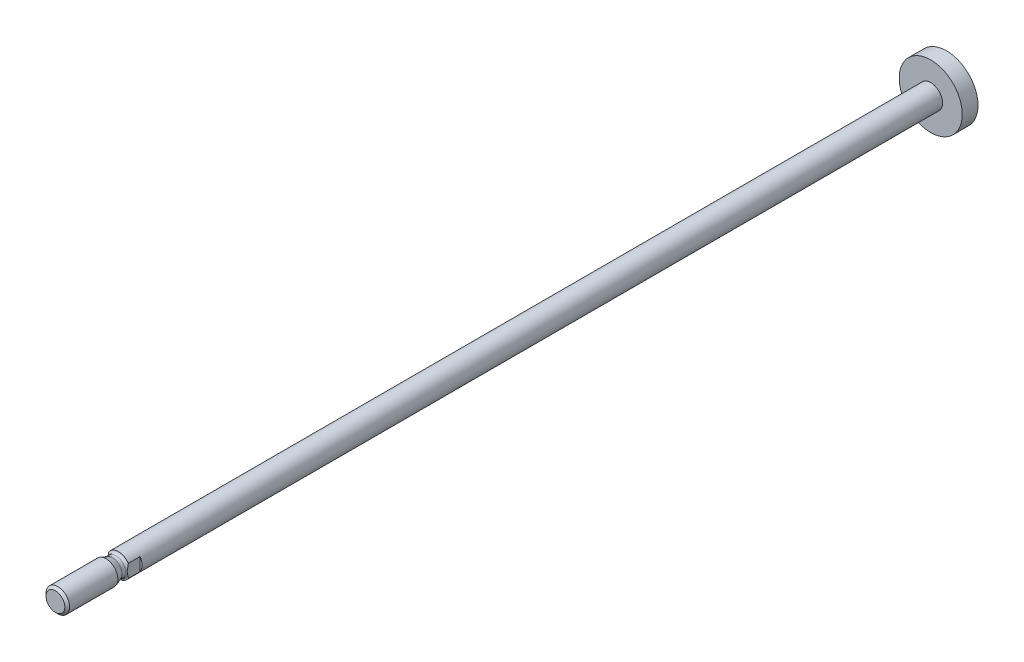
SolidWorks part; units mm, degrees
ref_plane "Ebene vorne" through (0, 0, 0) normal (0, 0, 1) x (1, 0, 0)
ref_plane "Ebene oben" through (0, 0, 0) normal (0, 1, 0) x (1, 0, 0)
ref_plane "Ebene rechts" through (0, 0, 0) normal (1, 0, 0) x (0, 0, -1)
sketch "Skizze1" plane through (0, 0, 0) normal (1, 0, 0) x (0, 0, -1)
  line L0 (-5, 0) -> (-5, 3)
  line L1 (-5, 3) -> (201.2, 3)
  line L2 (201.2, 3) -> (201.2, 8)
  line L3 (201.2, 8) -> (205.2, 8)
  line L4 (205.2, 8) -> (205.2, 0)
  line L5 (205.2, 0) -> (-5, 0)
  line L6 (205.2, 0) -> (-5, 0) construction
revolve "Rotation1" add sketch "Skizze1" angle 360 about L6 reverse direction yes
sketch "Skizze2" plane through (0, 0, 0) normal (1, 0, 0) x (0, 0, -1)
  line L0 (-21, 0) -> (-21, 2.3865)
  line L1 (-21, 2.3865) -> (-20.3865, 3)
  line L2 (-20.3865, 3) -> (-8.1485, 3)
  line L3 (-8.1485, 3) -> (-6.5994, 2.4362)
  line L4 (-6.3942, 2.4) -> (-5.6, 2.4)
  line L5 (-5, 3) -> (-4, 3)
  line L6 (-4, 3) -> (-4, 0)
  line L7 (-4, 0) -> (-21, 0)
  line L8 (-4, 0) -> (-21, 0) construction
  arc A0 (-6.5994, 2.4362) -> (-6.3942, 2.4) centre (-6.3942, 3) ccw
  arc A1 (-5.6, 2.4) -> (-5, 3) centre (-5.6, 3) ccw
revolve "Rotation2" add sketch "Skizze2" angle 360 about L8 reverse direction yes
cosmetic thread "Gewindedarstellung1" parameters "D1"=12.8515, "D2"=4.773
ref_plane "Ebene1" through (0, 0, 5) normal (0, 0, 1) x (1, 0, 0)
ref_plane "Ebene2" through (0, 0, 2) normal (0, 0, 1) x (1, 0, 0)
sketch "Skizze3" plane through (0, 0, 2) normal (0, 0, 1) x (1, 0, 0)
  line L0 (-5, 10) -> (-5, -5)
  line L1 (-5, -5) -> (-2.5, -5)
  line L2 (-2.5, -5) -> (-2.5, 5)
  line L3 (-2.5, 5) -> (2.5, 5)
  line L4 (2.5, 5) -> (2.5, -5)
  line L5 (2.5, -5) -> (5, -5)
  line L6 (5, -5) -> (5, 10)
  line L7 (5, 10) -> (-5, 10)
extrude "Schnitt-Linear austragen1" cut sketch "Skizze3" along normal blind 4
ref_plane "Ebene3" through (0, 0, -415) normal (0, 0, 1) x (1, 0, 0)
ref_plane "Ebene4" through (0, 0, 16) normal (0, 0, 1) x (1, 0, 0)
ref_plane "Ebene5" through (0, 0, 11.2) normal (0, 0, 1) x (1, 0, 0)
ref_plane "FDT_KSAUFSATZ XY" through (0, 0, 11.2) normal (0, 0, 1) x (1, 0, 0)
ref_plane "FDT_KSAUFSATZ XZ" through (0, 0, 0) normal (0, 1, 0) x (1, 0, 0)
ref_plane "FDT_KSAUFSATZ YZ" through (0, 0, 0) normal (-1, 0, 0) x (0, 0, 1)
ref_axis "FDT_KSAUFSATZ X" through (80.9, 0, 11.2) along (-1, 0, 0)
ref_axis "FDT_KSAUFSATZ Y" through (0, 50, 11.2) along (0, -1, 0)
ref_axis "FDT_KSAUFSATZ Z" through (0, 0, 80.9) along (0, 0, -1)
sketch3d "FDT_KSAUFSATZ"
  point P0 (0, 0, 11.2)
ref_plane "FDT_NUT XY" through (0, 0, 11.2) normal (0, 0, 1) x (1, 0, 0)
ref_plane "FDT_NUT XZ" through (0, 0, 0) normal (0, 1, 0) x (1, 0, 0)
ref_plane "FDT_NUT YZ" through (0, 0, 0) normal (-1, 0, 0) x (0, 0, 1)
ref_axis "FDT_NUT X" through (80.9, 0, 11.2) along (-1, 0, 0)
ref_axis "FDT_NUT Y" through (0, 50, 11.2) along (0, -1, 0)
ref_axis "FDT_NUT Z" through (0, 0, 80.9) along (0, 0, -1)
sketch3d "FDT_NUT"
  point P0 (0, 0, 11.2)
ref_plane "KS XY" through (0, 0, 0) normal (0, 0, -1) x (-1, 0, 0)
ref_plane "KS XZ" through (0, 0, 0) normal (0, 1, 0) x (1, 0, 0)
ref_plane "KS YZ" through (0, 0, 0) normal (1, 0, 0) x (0, 0, -1)
ref_axis "KS X" through (-80.9, 0, 0) along (1, 0, 0)
ref_axis "KS Y" through (0, 50, 0) along (0, -1, 0)
ref_axis "KS Z" through (0, 0, -80.9) along (0, 0, 1)
sketch3d "KS"
  point P0 (0, 0, 0)
ref_plane "NUT1 XY" through (0, 0, 16) normal (0, 0, 1) x (1, 0, 0)
ref_plane "NUT1 XZ" through (0, 0, 0) normal (0, -1, 0) x (-1, 0, 0)
ref_plane "NUT1 YZ" through (0, 0, 0) normal (1, 0, 0) x (0, 0, -1)
ref_axis "NUT1 X" through (-80.9, 0, 16) along (1, 0, 0)
ref_axis "NUT1 Y" through (0, -50, 16) along (0, 1, 0)
ref_axis "NUT1 Z" through (0, 0, 80.9) along (0, 0, -1)
sketch3d "NUT1"
  point P0 (0, 0, 16)
